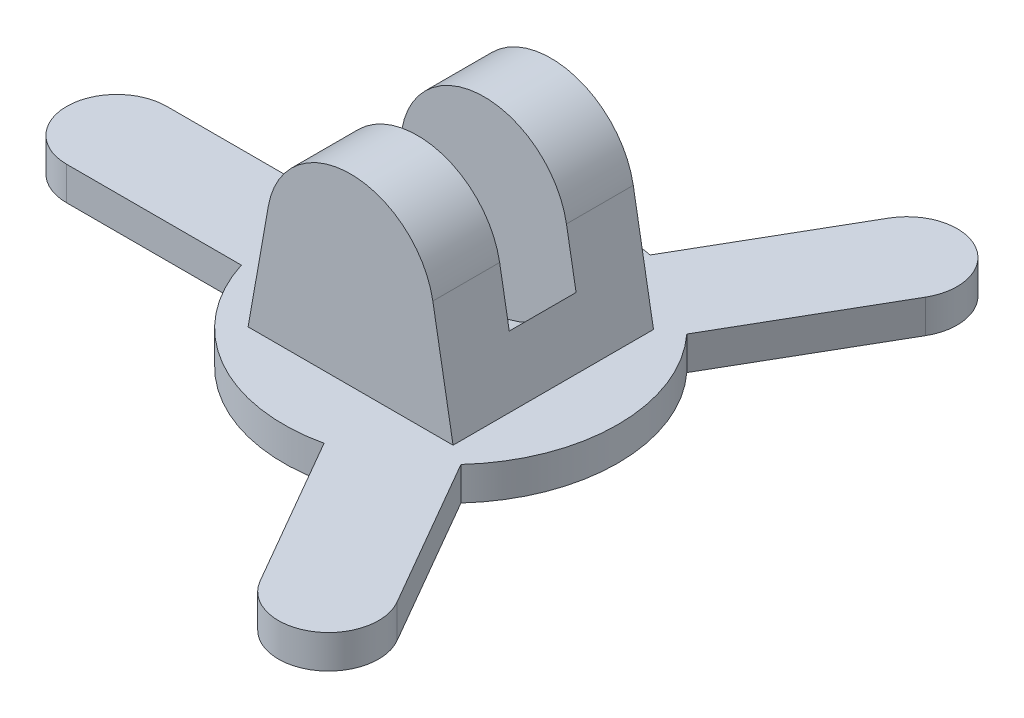
SolidWorks part; units mm, degrees
ref_plane "Front Plane" through (0, 0, 0) normal (0, 0, 1) x (1, 0, 0)
ref_plane "Top Plane" through (0, 0, 0) normal (0, 1, 0) x (1, 0, 0)
ref_plane "Right Plane" through (0, 0, 0) normal (1, 0, 0) x (0, 0, -1)
sketch "Sketch1" plane through (0, 0, 0) normal (0, 0, 1) x (1, 0, 0)
  line L0 (-12.3101, 2.1706) -> (-15.3377, -15)
  line L1 (-15.3377, -15) -> (15.3377, -15)
  line L2 (15.3377, -15) -> (12.3101, 2.1706)
  line L3 (-12.3101, 2.1706) -> (12.3101, 2.1706) construction
  arc A0 (12.3101, 2.1706) -> (-12.3101, 2.1706) centre (0, 0) ccw
  arc A1 (-12.3101, 2.1706) -> (12.3101, 2.1706) centre (0, 0) ccw
  point P6 (-17.3716, -15)
  point P16 (0, -15)
  dimension "D1" = 25
  dimension "D2" = 15
  dimension "D3" = 80
extrude "Boss-Extrude1" add sketch "Sketch1" along normal mid plane 30 contours L3 A1 | A0 L3 | A1 L0 L1 L2 region at (0, -12.8515, 0) region at (0, 6.496, 0) region at (0, -4.1534, 0)
extrude "Cut-Extrude1" cut sketch "Sketch1<3>" against normal mid plane 10 contours A0 L3 | L3 A1 region at (0, 6.496, 0) region at (0, -4.1534, 0)
sketch "Sketch1<3>" plane through (0, 0, 0) normal (0, 0, 1) x (1, 0, 0) same geometry as "Sketch1"
sketch "Sketch2" plane through (0, -15, 0) normal (0, -1, 0) x (1, 0, 0)
  line L0 (0, 0) -> (-50, 0) construction
  line L1 (0, -7.5) -> (-50, -7.5)
  line L2 (0, 7.5) -> (-50, 7.5)
  line L3 (6.4952, -3.75) -> (31.4952, 39.5513)
  line L4 (-6.4952, 3.75) -> (18.5048, 47.0513)
  line L5 (0, 0) -> (25, 43.3013) construction
  line L6 (-6.4952, -3.75) -> (18.5048, -47.0513)
  line L7 (6.4952, 3.75) -> (31.4952, -39.5513)
  line L8 (0, 0) -> (25, -43.3013) construction
  circle A0 centre (0, 0) radius 25
  arc A1 (0, -7.5) -> (0, 7.5) centre (0, 0) ccw
  arc A2 (-50, 7.5) -> (-50, -7.5) centre (-50, 0) ccw
  arc A3 (-6.4952, 3.75) -> (6.4952, -3.75) centre (0, 0) ccw
  arc A4 (31.4952, 39.5513) -> (18.5048, 47.0513) centre (25, 43.3013) ccw
  arc A5 (6.4952, 3.75) -> (-6.4952, -3.75) centre (0, 0) ccw
  arc A6 (18.5048, -47.0513) -> (31.4952, -39.5513) centre (25, -43.3013) ccw
  point P3 (-25, 0)
  point P9 (12.5, 21.6506)
  point P17 (12.5, -21.6506)
  point P23 (0, 0)
  line M7 (-15.3377, -15) -> (15.3377, -15)
  line M8 (15.3377, -15) -> (15.3377, 15)
  line M9 (15.3377, 15) -> (-15.3377, 15)
  line M10 (-15.3377, 15) -> (-15.3377, -15)
  dimension "D1" = 50
  dimension "D3" = 7.5
  dimension "D2" = 50
  dimension "D4" = 3
extrude "Boss-Extrude2" add sketch "Sketch2" along normal blind 5 contours L2 A2 L1 A0 | L2 A0 L1 M10 | L4 A0 L2 M10 M9 | L3 A4 L4 A0 | L3 A0 L4 M9 M8 | L7 A0 L3 M8 | A1 L1 L6 L7 L3 M7 M8 | L6 A0 L7 M8 M7 | L6 A6 L7 A0 | L1 A0 L6 M7 M10 | L6 L1 M10 M7 | A3 L4 L2 L1 L6 M10 | L2 L4 M9 M10 | A1 L7 L3 L4 L2 M8 M9 | L3 L7 M8 | A1 L3 L7 | A1 A5 A3 | A3 L6 L1 | A5 L2 L4 region at (6.6806, -15, -9.8576) region at (0, -15, 0) region at (-3.8759, -15, -6.7132) region at (-8.6921, -15, -11.4555) region at (-10.7595, -15, 0) region at (7.7517, -15, 0) region at (-9.147, -15, -17.4678) region at (-19.9851, -15, 0) region at (9.202, -15, -18.3971) region at (6.6806, -15, 9.8576) region at (13.1119, -15, 0) region at (-3.8759, -15, 6.7132) region at (-40.2981, -15, 0) region at (-8.6921, -15, 11.4555) region at (-9.147, -15, 17.4678) region at (20.149, -15, -34.8991) region at (9.202, -15, 18.3971) region at (19.5846, -15, 0) region at (20.149, -15, 34.8991)
sketch "Sketch3" plane through (0, 0, -5) normal (0, 0, 1) x (1, 0, 0)
  circle A0 centre (0, 0) radius 15
  dimension "D1" = 30
extrude "Cut-Extrude2" cut sketch "Sketch3" along normal up to surface (10 mm away) up to face at (0, 0, 5)
